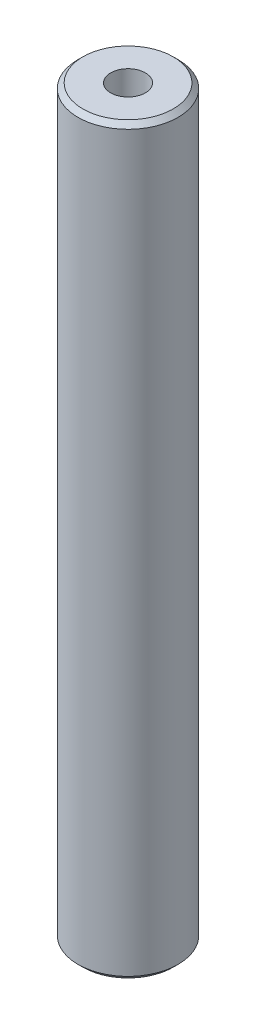
SolidWorks part; units mm, degrees
ref_plane "Front Plane" through (0, 0, 0) normal (0, 0, 1) x (1, 0, 0)
ref_plane "Top Plane" through (0, 0, 0) normal (0, 1, 0) x (1, 0, 0)
ref_plane "Right Plane" through (0, 0, 0) normal (1, 0, 0) x (0, 0, -1)
sketch "Sketch1" plane through (0, 0, 0) normal (0, 1, 0) x (1, 0, 0)
  circle A0 centre (0, 0) radius 37.5
  dimension "SHAFT_OD" = 75
extrude "Boss-Extrude1" add sketch "Sketch1" along normal blind 556.9307
sketch "Sketch2" plane through (0, 0, 0) normal (0, 1, 0) x (1, 0, 0)
  circle A0 centre (0, 0) radius 13.012
  dimension "BORE_D" = 26.0239
extrude "Cut-Extrude1" cut sketch "Sketch2" along normal through all
chamfer "Chamfer1" distance 3.6402 angle 45 2 edges at (0, 556.9307, 37.5) (0, 0, 37.5)
